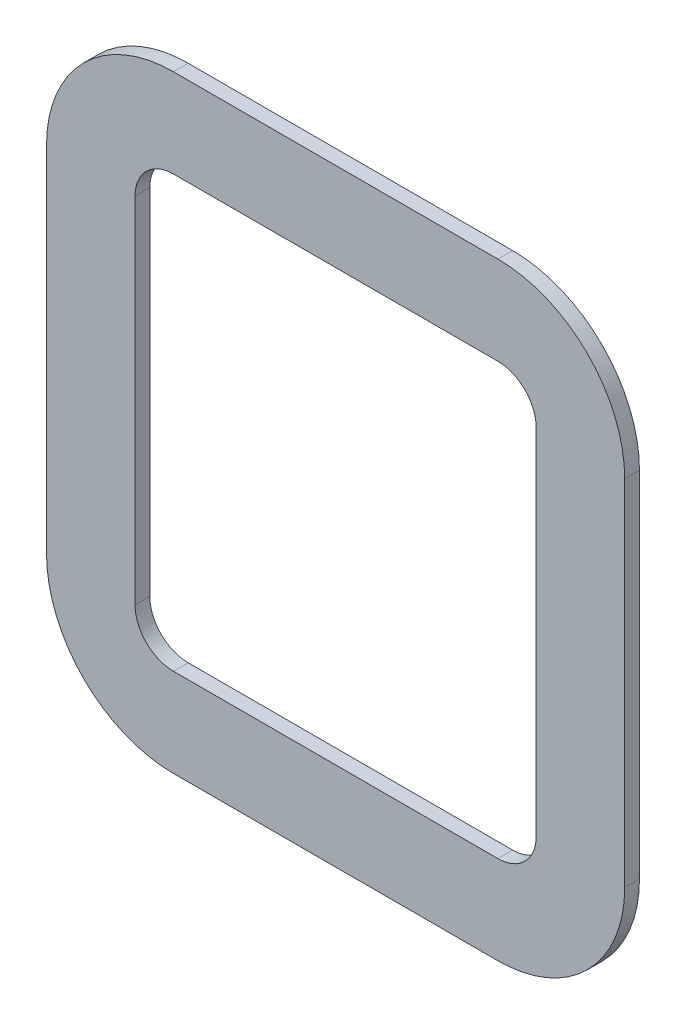
SolidWorks part; units mm, degrees
ref_plane "Front" through (0, 0, 0) normal (0, 0, 1) x (1, 0, 0)
ref_plane "Top" through (0, 0, 0) normal (0, 1, 0) x (1, 0, 0)
ref_plane "Right" through (0, 0, 0) normal (1, 0, 0) x (0, 0, -1)
ref_axis "X Axis" through (-10.78, 0, 0) along (1, 0, 0)
ref_axis "Y Axis" through (0, -11.33, 0) along (0, 1, 0)
ref_axis "Z Axis" through (0, 0, 0.025) along (0, 0, -1)
sketch "Sketch1" plane through (0, 0, 0) normal (0, 0, 1) x (1, 0, 0)
  line L4 (5.5, 10.3) -> (-5.5, 10.3)
  line L5 (-9.8, 6) -> (-9.8, -6)
  line L6 (5.5, -10.3) -> (-5.5, -10.3)
  line L7 (9.8, 6) -> (9.8, -6)
  line L10 (0, 7) -> (0, -7) construction
  line L11 (-4.115, 0) -> (3.9902, 0) construction
  line L12 (5.5, 7.3) -> (-5.5, 7.3)
  line L13 (5.5, 7) -> (-5.5, 7) construction
  line L14 (6.5, 6) -> (6.5, -6) construction
  line L15 (5.5, -7) -> (-5.5, -7) construction
  line L16 (-6.5, 6) -> (-6.5, -6) construction
  line L17 (-6.8, 6) -> (-6.8, -6)
  line L18 (5.5, -7.3) -> (-5.5, -7.3)
  line L19 (6.8, 6) -> (6.8, -6)
  arc A16 (-5.5, -7) -> (-6.5, -6) centre (-5.5, -6) cw construction
  arc A17 (-6.5, 6) -> (-5.5, 7) centre (-5.5, 6) cw construction
  arc A18 (6.5, -6) -> (5.5, -7) centre (5.5, -6) cw construction
  arc A19 (6.5, 6) -> (5.5, 7) centre (5.5, 6) ccw construction
  arc A20 (-6.8, 6) -> (-5.5, 7.3) centre (-5.5, 6) cw
  arc A21 (-5.5, -7.3) -> (-6.8, -6) centre (-5.5, -6) cw
  arc A22 (6.8, -6) -> (5.5, -7.3) centre (5.5, -6) cw
  arc A23 (6.8, 6) -> (5.5, 7.3) centre (5.5, 6) ccw
  arc A24 (-9.8, 6) -> (-5.5, 10.3) centre (-5.5, 6) cw
  arc A25 (-5.5, -10.3) -> (-9.8, -6) centre (-5.5, -6) cw
  arc A26 (9.8, -6) -> (5.5, -10.3) centre (5.5, -6) cw
  arc A27 (9.8, 6) -> (5.5, 10.3) centre (5.5, 6) ccw
extrude "Boss-Extrude1" add sketch "Sketch1" against normal blind 0.5
